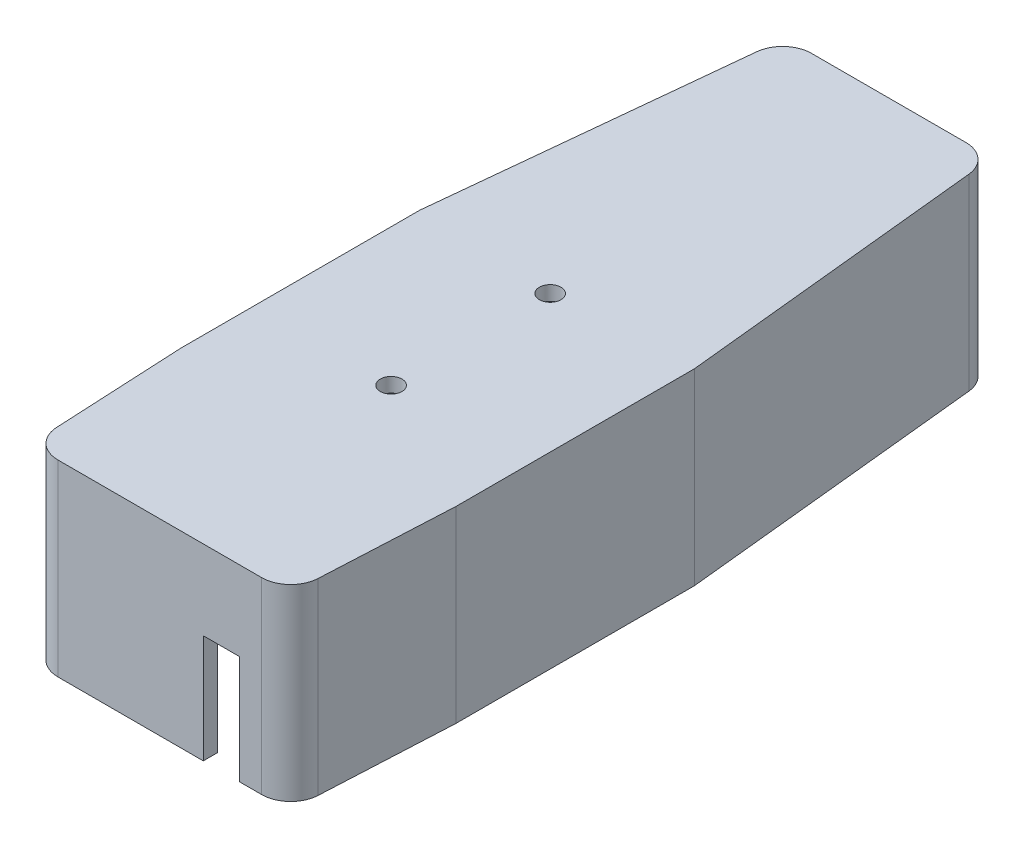
SolidWorks part; units mm, degrees
ref_plane "Front Plane" through (0, 0, 0) normal (0, 0, 1) x (1, 0, 0)
ref_plane "Top Plane" through (0, 0, 0) normal (0, 1, 0) x (1, 0, 0)
ref_plane "Right Plane" through (0, 0, 0) normal (1, 0, 0) x (0, 0, -1)
sketch "Sketch1" plane through (0, 0, 0) normal (0, 1, 0) x (1, 0, 0)
  line L8 (6.3059, 78.848) -> (27.6941, 78.848)
  line L9 (31.6734, 75.255) -> (36, 32.95)
  line L10 (36, -0.05) -> (36, 32.95)
  line L11 (35.0925, -18.1998) -> (36, -0.05)
  line L12 (2.9025, -22) -> (31.0975, -22)
  line L13 (-2, -0.05) -> (-1.0925, -18.1998)
  line L14 (-2, -0.05) -> (-2, 32.95)
  line L15 (2.3266, 75.255) -> (-2, 32.95)
  arc A4 (31.6734, 75.255) -> (27.6941, 78.848) centre (27.6941, 74.848) ccw
  arc A5 (31.0975, -22) -> (35.0925, -18.1998) centre (31.0975, -18) ccw
  arc A6 (-1.0925, -18.1998) -> (2.9025, -22) centre (2.9025, -18) ccw
  arc A7 (2.3266, 75.255) -> (6.3059, 78.848) centre (6.3059, 74.848) cw
  dimension "D1" = 33
  dimension "D2" = 33
extrude "Boss-Extrude1" add sketch "Sketch1" along normal blind 26
shell "Shell1" thickness 2 removed face at (17, 0, -24.4617)
sketch "Sketch3" plane through (0, 0, 22) normal (0, 0, 1) x (1, 0, 0)
  line L0 (28.0089, 0) -> (28.0089, 15)
  line L1 (2.9025, 0) -> (31.0975, 0) construction
  line L2 (23.0089, 0) -> (23.0089, 15)
  line L3 (28.0089, 0) -> (23.0089, 0)
  line L4 (28.0089, 15) -> (23.0089, 15)
  dimension "D1" = 0
  dimension "D2" = 5
extrude "Cut-Extrude1" cut sketch "Sketch3" against normal blind 5
sketch "Sketch4" plane through (0, 24, 0) normal (0, -1, 0) x (1, 0, 0)
  line L0 (0, -32.848) -> (0, 0) construction
  line L3 (2.9025, 20) -> (31.0975, 20) construction
  circle A0 centre (17, -10) radius 1.5
  circle A1 centre (17, -32) radius 1.5
  point P6 (17, 20)
  dimension "D3" = 3
  dimension "D4" = 3
  dimension "D1" = 22
  dimension "D2" = 17
  dimension "D5" = 30
extrude "Cut-Extrude2" cut sketch "Sketch4" against normal blind 10
sketch "Sketch5" plane through (0, 0, 0) normal (0, -1, 0) x (1, 0, 0)
  line L1 (30.5227, -66.848) -> (3.4773, -66.848)
  line L2 (34, -32.848) -> (29.6837, -75.0515) construction
  line L3 (4.3163, -75.0515) -> (0, -32.848) construction
  line L4 (27.6941, -76.848) -> (6.3059, -76.848) construction
  line L5 (30.5227, -66.848) -> (29.6837, -75.0515)
  line L6 (27.6941, -76.848) -> (6.3059, -76.848)
  line L7 (4.3163, -75.0515) -> (3.4773, -66.848)
  arc A1 (27.6941, -76.848) -> (29.6837, -75.0515) centre (27.6941, -74.848) ccw construction
  arc A2 (27.6941, -76.848) -> (29.6837, -75.0515) centre (27.6941, -74.848) ccw
  arc A3 (4.3163, -75.0515) -> (6.3059, -76.848) centre (6.3059, -74.848) ccw construction
  arc A4 (4.3163, -75.0515) -> (6.3059, -76.848) centre (6.3059, -74.848) ccw
  dimension "D2" = 10
extrude "Boss-Extrude2" add sketch "Sketch5" against normal blind 3
sketch "Sketch7" plane through (0, 0, 0) normal (0, -1, 0) x (1, 0, 0)
  circle A0 centre (24.3355, -71.848) radius 1.397
extrude "Cut-Extrude3" cut sketch "Sketch7" against normal blind 5
sketch "Sketch8" plane through (0, 0, 0) normal (0, -1, 0) x (1, 0, 0)
  circle A0 centre (9.3362, -71.848) radius 1.397
extrude "Cut-Extrude4" cut sketch "Sketch8" against normal blind 5
